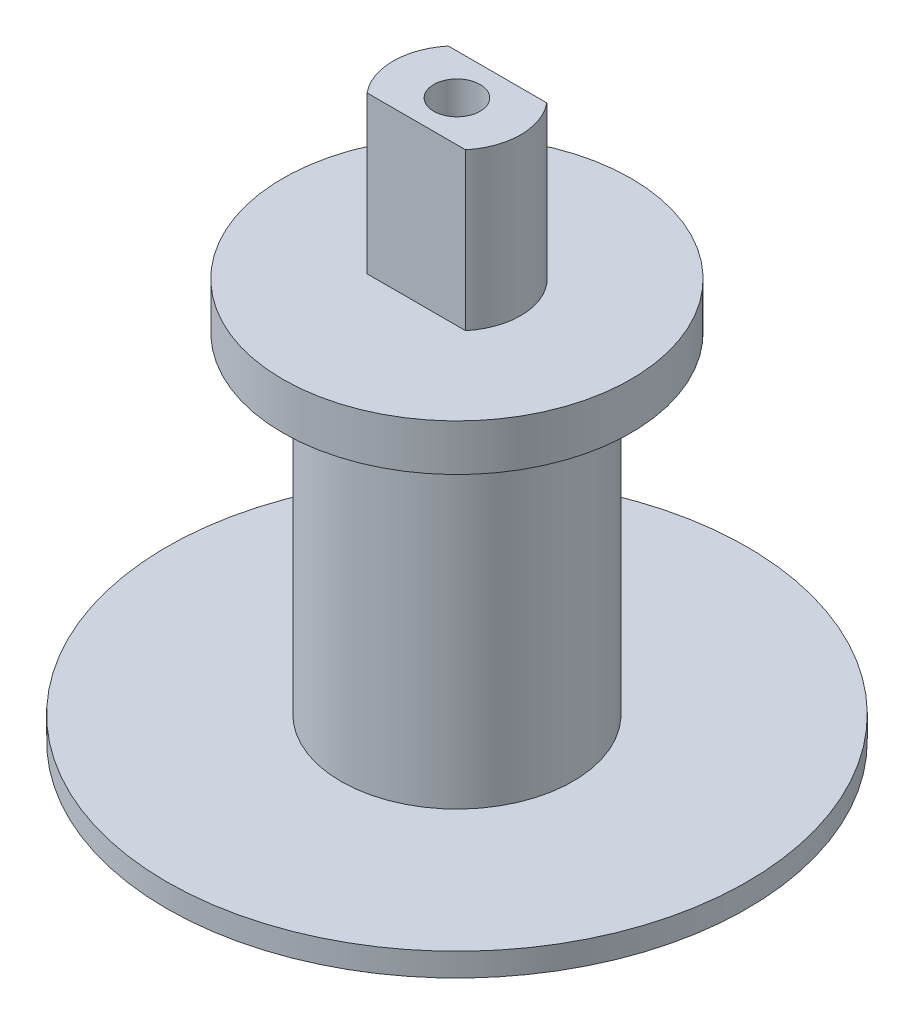
SolidWorks part; units mm, degrees
ref_plane "Front Plane" through (0, 0, 0) normal (0, 0, 1) x (1, 0, 0)
ref_plane "Top Plane" through (0, 0, 0) normal (0, 1, 0) x (1, 0, 0)
ref_plane "Right Plane" through (0, 0, 0) normal (1, 0, 0) x (0, 0, -1)
sketch "Sketch1" plane through (0, 0, 0) normal (0, 1, 0) x (1, 0, 0)
  circle A0 centre (0, 0) radius 10
extrude "Boss-Extrude2" add sketch "Sketch1" along normal blind 1
sketch "Sketch3" plane through (0, 1, 0) normal (0, 1, 0) x (1, 0, 0)
  circle A0 centre (0, 0) radius 5
extrude "Boss-Extrude3" add sketch "Sketch3" along normal blind 14
sketch "Sketch4" plane through (0, 15, 0) normal (0, 1, 0) x (1, 0, 0)
  line L0 (0, 0) -> (0, 2) construction
  line L1 (0, 2) -> (0, -2) construction
  line L3 (0, 2) -> (-4.3147, 2)
  line L4 (0, -2) -> (3.8775, -2)
  line L5 (0, -2) -> (0, 2)
  line L6 (0, 2) -> (3.8775, 2)
  line L7 (3.8775, -2) -> (3.8775, 2)
  line L8 (0, 2) -> (0, -2)
  line L9 (0, -2) -> (-4.3147, -2)
  line L10 (-4.3147, 2) -> (-4.3147, -2)
  circle A0 centre (0, 0) radius 3
extrude "Cut-Extrude1" cut sketch "Sketch4" against normal blind 19 contours L3 A0 L9 L5 | L4 A0 L6 L5 region at (-1.3889, 15, 0) region at (1.3889, 15, 0)
sketch "Sketch5" plane through (0, 1, 0) normal (0, 1, 0) x (1, 0, 0)
  circle A0 centre (0, 0) radius 12.5
extrude "Boss-Extrude4" add sketch "Sketch5" against normal up to surface (1 mm away) up to face at (0, 0, 0)
sketch "Sketch6" plane through (0, 1, 0) normal (0, 1, 0) x (1, 0, 0)
  line L4 (2.2361, 2) -> (-2.2361, 2)
  line L5 (-2.2361, -2) -> (2.2361, -2)
  line L6 (2.2361, 2) -> (-2.2361, 2)
  line L7 (-2.2361, -2) -> (2.2361, -2)
  arc A4 (-2.2361, 2) -> (-2.2361, -2) centre (0, 0) ccw
  arc A5 (2.2361, -2) -> (2.2361, 2) centre (0, 0) ccw
  arc A6 (-2.2361, 2) -> (-2.2361, -2) centre (0, 0) ccw
  arc A7 (2.2361, -2) -> (2.2361, 2) centre (0, 0) ccw
  dimension "D1" = 0
extrude "Cut-Extrude2" cut sketch "Sketch6" against normal blind 19
sketch "Sketch7" plane through (0, 15, 0) normal (0, 1, 0) x (1, 0, 0)
  line L4 (-2.2361, -2) -> (2.2361, -2)
  line L5 (2.2361, 2) -> (-2.2361, 2)
  line L6 (-2.2361, -2) -> (2.2361, -2)
  line L7 (2.2361, 2) -> (-2.2361, 2)
  circle A2 centre (0, 0) radius 5
  circle A3 centre (0, 0) radius 5
  arc A7 (2.2361, -2) -> (2.2361, 2) centre (0, 0) ccw
  arc A8 (-2.2361, 2) -> (-2.2361, -2) centre (0, 0) ccw
  arc A9 (2.2361, -2) -> (2.2361, 2) centre (0, 0) ccw
  arc A10 (-2.2361, 2) -> (-2.2361, -2) centre (0, 0) ccw
  dimension "D1" = 0
  dimension "D2" = 0
extrude "Boss-Extrude5" add sketch "Sketch7" along normal blind 2 separate body contours L6 A9 L7 A10
sketch "Sketch8" plane through (0, 17, 0) normal (0, 1, 0) x (1, 0, 0)
  circle A0 centre (0, 0) radius 7.5
extrude "Boss-Extrude6" add sketch "Sketch8" along normal blind 2
sketch "Sketch9" plane through (0, 19, 0) normal (0, 1, 0) x (1, 0, 0)
  circle A0 centre (0, 0) radius 1
extrude "Cut-Extrude3" cut sketch "Sketch9" against normal blind 25
sketch "Sketch10" plane through (0, 15, 0) normal (0, -1, 0) x (1, 0, 0)
  line L4 (-2.1213, -1.75) -> (2.1213, -1.75)
  line L5 (2.1213, 1.75) -> (-2.1213, 1.75)
  line L6 (-2.1213, -1.75) -> (2.1213, -1.75)
  line L7 (2.1213, 1.75) -> (-2.1213, 1.75)
  arc A4 (-2.1213, 1.75) -> (-2.1213, -1.75) centre (0, 0) ccw
  arc A5 (2.1213, -1.75) -> (2.1213, 1.75) centre (0, 0) ccw
  arc A6 (-2.1213, 1.75) -> (-2.1213, -1.75) centre (0, 0) ccw
  arc A7 (2.1213, -1.75) -> (2.1213, 1.75) centre (0, 0) ccw
  dimension "D1" = 0.25
extrude "Cut-Extrude4" cut sketch "Sketch10" against normal up to surface (2 mm away) up to face at (0, 17, 7.5)
sketch "Sketch11" plane through (0, 17, 0) normal (0, -1, 0) x (1, 0, 0)
  line L4 (-2.1213, -1.75) -> (2.1213, -1.75)
  line L5 (2.1213, 1.75) -> (-2.1213, 1.75)
  line L6 (-2.1213, -1.75) -> (2.1213, -1.75)
  line L7 (2.1213, 1.75) -> (-2.1213, 1.75)
  arc A4 (-2.1213, 1.75) -> (-2.1213, -1.75) centre (0, 0) ccw
  arc A5 (2.1213, -1.75) -> (2.1213, 1.75) centre (0, 0) ccw
  arc A6 (-2.1213, 1.75) -> (-2.1213, -1.75) centre (0, 0) ccw
  arc A7 (2.1213, -1.75) -> (2.1213, 1.75) centre (0, 0) ccw
  dimension "D1" = 0
extrude "Boss-Extrude7" add sketch "Sketch11" along normal blind 10
sketch "Sketch12" plane through (0, 0, 0) normal (0, -1, 0) x (1, 0, 0)
  circle A0 centre (0, 0) radius 4
  circle A3 centre (0, 0) radius 12.5
  circle A4 centre (0, 0) radius 12.5
  dimension "D1" = 0
sketch "Sketch14" plane through (0, 17, 0) normal (0, 1, 0) x (1, 0, 0)
  circle A2 centre (0, 0) radius 1
  circle A3 centre (0, 0) radius 1
  dimension "D1" = 0
extrude "Cut-Extrude5" cut sketch "Sketch14" against normal blind 18
sketch "Sketch15" plane through (0, 7, 0) normal (0, -1, 0) x (1, 0, 0)
  line L4 (-2.1213, -1.75) -> (2.1213, -1.75)
  line L5 (2.1213, 1.75) -> (-2.1213, 1.75)
  line L6 (-2.1213, -1.75) -> (2.1213, -1.75)
  line L7 (2.1213, 1.75) -> (-2.1213, 1.75)
  arc A4 (-2.1213, 1.75) -> (-2.1213, -1.75) centre (0, 0) ccw
  arc A5 (2.1213, -1.75) -> (2.1213, 1.75) centre (0, 0) ccw
  arc A6 (-2.1213, 1.75) -> (-2.1213, -1.75) centre (0, 0) ccw
  arc A7 (2.1213, -1.75) -> (2.1213, 1.75) centre (0, 0) ccw
  circle A8 centre (0, 0) radius 1
  circle A9 centre (0, 0) radius 1
  dimension "D1" = 0
  dimension "D2" = 0
extrude "Boss-Extrude8" add sketch "Sketch15" against normal blind 17
sketch "Sketch16" plane through (0, 7, 0) normal (0, -1, 0) x (1, 0, 0)
  line L4 (-2.1213, -1.75) -> (2.1213, -1.75)
  line L5 (2.1213, 1.75) -> (-2.1213, 1.75)
  line L6 (-2.1213, -1.75) -> (2.1213, -1.75)
  line L7 (2.1213, 1.75) -> (-2.1213, 1.75)
  arc A4 (-2.1213, 1.75) -> (-2.1213, -1.75) centre (0, 0) ccw
  arc A5 (2.1213, -1.75) -> (2.1213, 1.75) centre (0, 0) ccw
  arc A6 (-2.1213, 1.75) -> (-2.1213, -1.75) centre (0, 0) ccw
  arc A7 (2.1213, -1.75) -> (2.1213, 1.75) centre (0, 0) ccw
  circle A8 centre (0, 0) radius 1
  circle A9 centre (0, 0) radius 1
  dimension "D1" = 0
  dimension "D2" = 0
extrude "Cut-Extrude7" cut sketch "Sketch16" against normal up to surface (10 mm away) up to face at (0, 17, 7.5)
sketch "Sketch17" plane through (0, 15, 0) normal (0, -1, 0) x (1, 0, 0)
  line L4 (-2.2361, -2) -> (2.2361, -2)
  line L5 (2.2361, 2) -> (-2.2361, 2)
  line L6 (-2.2361, -2) -> (2.2361, -2)
  line L7 (2.2361, 2) -> (-2.2361, 2)
  arc A4 (-2.2361, 2) -> (-2.2361, -2) centre (0, 0) ccw
  arc A5 (2.2361, -2) -> (2.2361, 2) centre (0, 0) ccw
  arc A6 (-2.2361, 2) -> (-2.2361, -2) centre (0, 0) ccw
  arc A7 (2.2361, -2) -> (2.2361, 2) centre (0, 0) ccw
  dimension "D1" = 0
extrude "Cut-Extrude8" cut sketch "Sketch17" against normal up to surface (2 mm away) up to face at (0, 17, 7.5)
sketch "Sketch18" plane through (0, 17, 0) normal (0, -1, 0) x (1, 0, 0)
  circle A2 centre (0, 0) radius 7.5
  circle A3 centre (0, 0) radius 7.5
  dimension "D1" = 0
extrude "Boss-Extrude9" add sketch "Sketch18" along normal blind 1.75
sketch "Sketch19" plane through (0, 19, 0) normal (0, 1, 0) x (1, 0, 0)
  line L9 (2.1213, 1.75) -> (-2.1213, 1.75)
  line L10 (-2.1213, -1.75) -> (2.1213, -1.75)
  line L11 (2.1213, 1.75) -> (-2.1213, 1.75)
  line L12 (-2.1213, -1.75) -> (2.1213, -1.75)
  circle A0 centre (0, 0) radius 6.5
  circle A2 centre (0, 0) radius 7.5
  circle A3 centre (0, 0) radius 7.5
  arc A11 (-2.1213, 1.75) -> (-2.1213, -1.75) centre (0, 0) ccw
  arc A12 (2.1213, -1.75) -> (2.1213, 1.75) centre (0, 0) ccw
  arc A13 (-2.1213, 1.75) -> (-2.1213, -1.75) centre (0, 0) ccw
  arc A14 (2.1213, -1.75) -> (2.1213, 1.75) centre (0, 0) ccw
  arc M7 (-2.1213, -1.75) -> (-2.1213, 1.75) centre (0, 0) cw
  line M8 (-2.1213, 1.75) -> (2.1213, 1.75)
  arc M9 (2.1213, 1.75) -> (2.1213, -1.75) centre (0, 0) cw
  line M10 (2.1213, -1.75) -> (-2.1213, -1.75)
  circle M11 centre (0, 0) radius 7.5
  dimension "D1" = 0
  dimension "D2" = 1
  dimension "D3" = 0
extrude "Cut-Extrude9" cut sketch "Sketch19" against normal blind 1.75 contours A0 M11 | A0 M10 M7 M8 M9 region at (-6.3162, 19, 0) region at (-7.2879, 19, 0)
